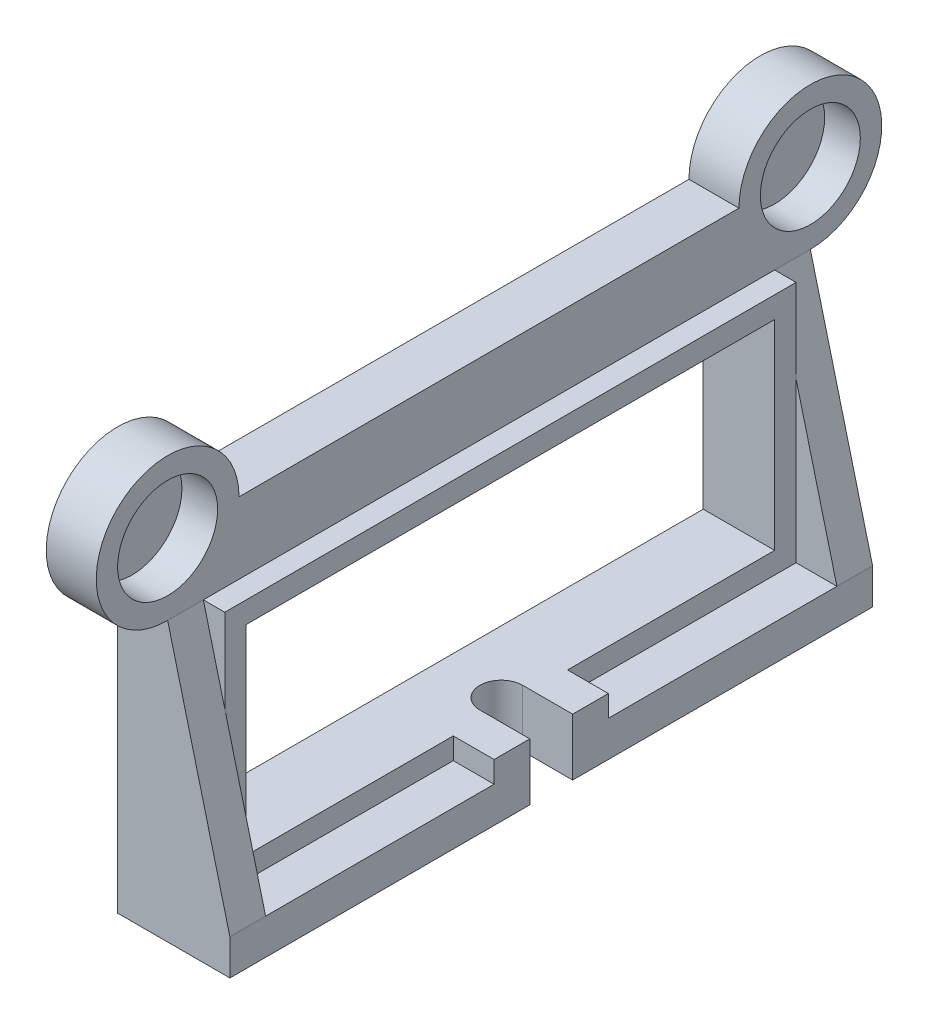
SolidWorks part; units mm, degrees
material "6061-T6 (SS)"
ref_plane "Ön Düzlem" through (0, 0, 0) normal (0, 0, 1) x (1, 0, 0)
ref_plane "Üst Düzlem" through (0, 0, 0) normal (0, 1, 0) x (1, 0, 0)
ref_plane "Sağ Düzlem" through (0, 0, 0) normal (1, 0, 0) x (0, 0, -1)
sketch "Sketch1" plane through (0, 0, 0) normal (1, 0, 0) x (0, 0, -1)
  line L0 (10, 0) -> (80, 0)
  line L4 (0, -10) -> (0, -49)
  line L5 (0, -49) -> (90, -49)
  line L6 (90, -49) -> (90, -10)
  circle A2 centre (0, 0) radius 10
  circle A3 centre (90, 0) radius 10
  dimension "D1" = 39
  dimension "D4" = 20
  dimension "D5" = 20
  dimension "D3" = 90
extrude "Boss-Extrude2" add sketch "Sketch1" along normal blind 7 contours A2 | A3 L4 region at (0, 0, 0) region at (0, 0, -90)
extrude "Boss-Extrude3" add sketch "Sketch1<3>" along normal blind 17 contours A3 L0 A2 L4 L5 L6 region at (0, -25.2481, -45)
sketch "Sketch1<3>" plane through (0, 0, 0) normal (1, 0, 0) x (0, 0, -1) same geometry as "Sketch1"
sketch "Sketch3" plane through (17, 0, 0) normal (1, 0, 0) x (0, 0, -1)
  line L0 (0, -10) -> (90, -10)
  line L1 (10, 0) -> (80, 0)
  arc A0 (0, -10) -> (10, 0) centre (0, 0) ccw
  arc A1 (80, 0) -> (90, -10) centre (90, 0) ccw
extrude "Cut-Extrude1" cut sketch "Sketch3" against normal blind 10
sketch "Sketch4" plane through (0, 0, 0) normal (0, 0, 1) x (1, 0, 0)
  line L0 (7, -10) -> (17, -49)
  line L1 (17, -49) -> (17, -10)
  line L2 (17, -10) -> (7, -10) construction
  line L3 (17, -10) -> (17, -49) construction
  line L4 (17, -10) -> (7, -10)
extrude "Cut-Extrude2" cut sketch "Sketch4" against normal through all
sketch "Sketch5" plane through (7, 0, 0) normal (1, 0, 0) x (0, 0, -1)
  circle A0 centre (0, 0) radius 7
  circle A1 centre (90, 0) radius 7
  arc A2 (90, -10) -> (80, 0) centre (90, 0) ccw construction
  dimension "D1" = 14
  dimension "D2" = 14
extrude "Cut-Extrude3" cut sketch "Sketch5" against normal blind 5
sketch "Sketch6" plane through (0, 0, 0) normal (-1, 0, 0) x (0, 0, 1)
  line L0 (-85, -10) -> (-85, -44)
  line L1 (-85, -44) -> (-5, -44)
  line L2 (-85, -10) -> (-5, -10)
  line L3 (-5, -10) -> (-5, -44)
  line L4 (-90, -49) -> (-90, -10) construction
  line L5 (0, -10) -> (0, -49) construction
  line L6 (0, -49) -> (-90, -49) construction
  line L7 (-10, 0) -> (-80, 0) construction
  dimension "D1" = 5
  dimension "D2" = 5
  dimension "D3" = 5
  dimension "D4" = 10
extrude "Cut-Extrude4" cut sketch "Sketch6" against normal through all
sketch "Sketch7" plane through (0, 0, 0) normal (-1, 0, 0) x (0, 0, 1)
  line L0 (-82, -13) -> (-82, -41)
  line L1 (-82, -41) -> (-8, -41)
  line L2 (-8, -41) -> (-8, -13)
  line L3 (-8, -13) -> (-82, -13)
  line L4 (-85, -10) -> (-85, -44)
  line L5 (-85, -44) -> (-5, -44)
  line L6 (-5, -44) -> (-5, -10)
  line L7 (-5, -10) -> (-85, -10)
  dimension "D1" = 3
  dimension "D2" = 3
  dimension "D3" = 3
  dimension "D4" = 3
extrude "Boss-Extrude4" add sketch "Sketch7" against normal blind 10
sketch "Sketch8" plane through (0, 0, 0) normal (0, 0, 1) x (1, 0, 0)
  line L0 (15.7179, -44) -> (17, -49)
  line L1 (7, -10) -> (17, -49) construction
  line L2 (17, -49) -> (6.9679, -49)
  line L3 (17, -49) -> (0, -49) construction
  line L4 (6.9679, -49) -> (6.9679, -44)
  line L5 (6.9679, -44) -> (15.7179, -44)
  dimension "D1" = 8.75
extrude "Cut-Extrude5" cut sketch "Sketch8" against normal through all
sketch "Sketch9" plane through (6.9679, 0, 0) normal (1, 0, 0) x (0, 0, -1)
  line L0 (0, -44) -> (0, -49)
  line L1 (0, -49) -> (90, -49)
  line L2 (90, -49) -> (90, -44)
  line L3 (90, -44) -> (0, -44)
extrude "Boss-Extrude5" add sketch "Sketch9" along normal up to vertex (8.75 mm away) up to point (15.718, -44, -90)
sketch "Sketch10" plane through (15.7179, 0, 0) normal (1, 0, 0) x (0, 0, -1)
  line L0 (37, -44) -> (37, -41)
  line L1 (85, -44) -> (5, -44) construction
  line L2 (82, -41) -> (8, -41) construction
  line L3 (37, -41) -> (53, -41)
  line L4 (53, -41) -> (53, -44)
  line L6 (37, -44) -> (53, -44)
  dimension "D1" = 16
  dimension "D2" = 32
extrude "Boss-Extrude6" add sketch "Sketch10" against normal up to surface (8.7179 mm away)
sketch "Sketch11" plane through (0, -41, 0) normal (0, 1, 0) x (1, 0, 0)
  line L0 (15.7179, 42) -> (8.7179, 42)
  line L1 (15.7179, 53) -> (15.7179, 37) construction
  line L2 (15.7179, 48) -> (8.7179, 48)
  line L3 (15.7179, 48) -> (15.7179, 42)
  arc A0 (8.7179, 42) -> (8.7179, 48) centre (8.7179, 45) cw
  dimension "D1" = 6
  dimension "D2" = 7
  dimension "D3" = 5
extrude "Cut-Extrude6" cut sketch "Sketch11" against normal blind 11
